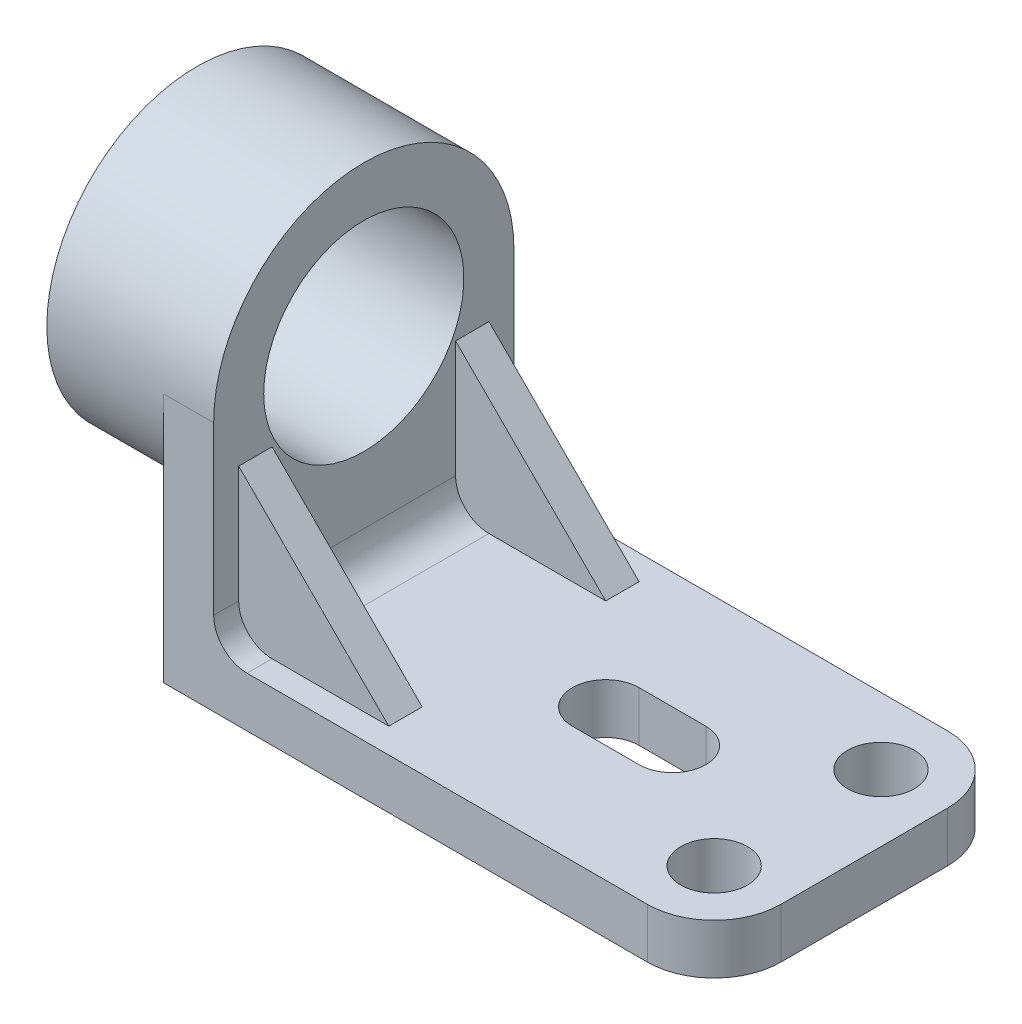
SolidWorks part; units mm, degrees
ref_plane "Front Plane" through (0, 0, 0) normal (0, 0, 1) x (1, 0, 0)
ref_plane "Top Plane" through (0, 0, 0) normal (0, 1, 0) x (1, 0, 0)
ref_plane "Right Plane" through (0, 0, 0) normal (1, 0, 0) x (0, 0, -1)
sketch "Sketch1" plane through (0, 0, 0) normal (0, 1, 0) x (1, 0, 0)
  line L0 (-6.7416, 0) -> (6.7416, 0) construction
  line L1 (-30, 18) -> (22, 18)
  line L2 (-30, 18) -> (-30, -18)
  line L3 (-30, -18) -> (22, -18)
  line L4 (30, 10) -> (30, -10)
  line L5 (-30, 18) -> (30, -18) construction
  line L6 (-30, -18) -> (30, 18) construction
  line L7 (-1, 0) -> (7, 0) construction
  line L8 (-1, 4) -> (7, 4)
  line L9 (-1, -4) -> (7, -4)
  circle A0 centre (22, -10) radius 4
  arc A1 (22, 18) -> (30, 10) centre (22, 10) cw
  arc A2 (22, -18) -> (30, -10) centre (22, -10) ccw
  circle A5 centre (22, 10) radius 4
  arc A6 (-1, 4) -> (-1, -4) centre (-1, 0) ccw
  arc A7 (7, -4) -> (7, 4) centre (7, 0) ccw
  point P0 (0, 0)
  point P15 (-32.4391, -17.6941)
  point P16 (-32.4391, 17.6941)
  point P17 (-33, -17.0777)
  point P18 (-33, 17.2577)
  point P25 (0, 0)
  point P26 (0, 0)
  point P27 (3, 0)
  point P32 (-6.7416, 0)
  dimension "D3" = 8
  dimension "D4" = 8
  dimension "D6" = 4
  dimension "D1" = 60
  dimension "D2" = 36
  dimension "D5" = 8
  dimension "D7" = 23
extrude "Boss-Extrude1" add sketch "Sketch1" along normal blind 6
sketch "Sketch2" plane through (-30, 0, 0) normal (-1, 0, 0) x (0, 0, 1)
  line L1 (-18, 0) -> (18, 0) construction
  line L10 (-18, 0) -> (-18, 30)
  line L11 (18, 0) -> (18, 30)
  line L12 (-18, 0) -> (18, 0)
  circle A0 centre (0, 30) radius 12
  arc A1 (18, 30) -> (-18, 30) centre (0, 30) ccw
  point P1 (-18, 0)
  point P2 (0, 0)
  point P4 (18, 0)
  dimension "D1" = 24
  dimension "D2" = 36
  dimension "D3" = 30
extrude "Boss-Extrude2" add sketch "Sketch2" along normal blind 6
sketch "Sketch3" plane through (-36, 0, 0) normal (-1, 0, 0) x (0, 0, 1)
  circle A0 centre (0, 30) radius 12 construction
  circle A1 centre (0, 30) radius 12
  circle A2 centre (0, 30) radius 18
  dimension "D1" = 36
extrude "Boss-Extrude3" add sketch "Sketch3" along normal blind 14
fillet "Fillet1" radius 4 1 edges at (-30, 6, 0)
ref_plane "Plane1" through (0, 0, 15) normal (0, 0, 1) x (1, 0, 0)
sketch "Sketch4" plane through (0, 0, 15) normal (0, 0, 1) x (1, 0, 0)
  line L0 (-26, 6) -> (22, 6) construction
  line L1 (-30, 10) -> (-30, 30) construction
  line L2 (-26, 6) -> (-12, 6)
  line L3 (-30, 10) -> (-30, 24)
  line L4 (-30, 24) -> (-12, 6)
  arc A0 (-30, 10) -> (-26, 6) centre (-26, 10) ccw construction
  arc A1 (-30, 10) -> (-26, 6) centre (-26, 10) ccw
  point P7 (-30, 27.897)
  dimension "D1" = 45
  dimension "D2" = 18
extrude "Boss-Extrude4" add sketch "Sketch4" against normal blind 4
ref_plane "Plane2" through (0, 0, 0) normal (0, 0, -1) x (-1, 0, 0)
mirror "Mirror1" about plane through (0, 0, 0) normal (0, 0, -1) of "Boss-Extrude4"
